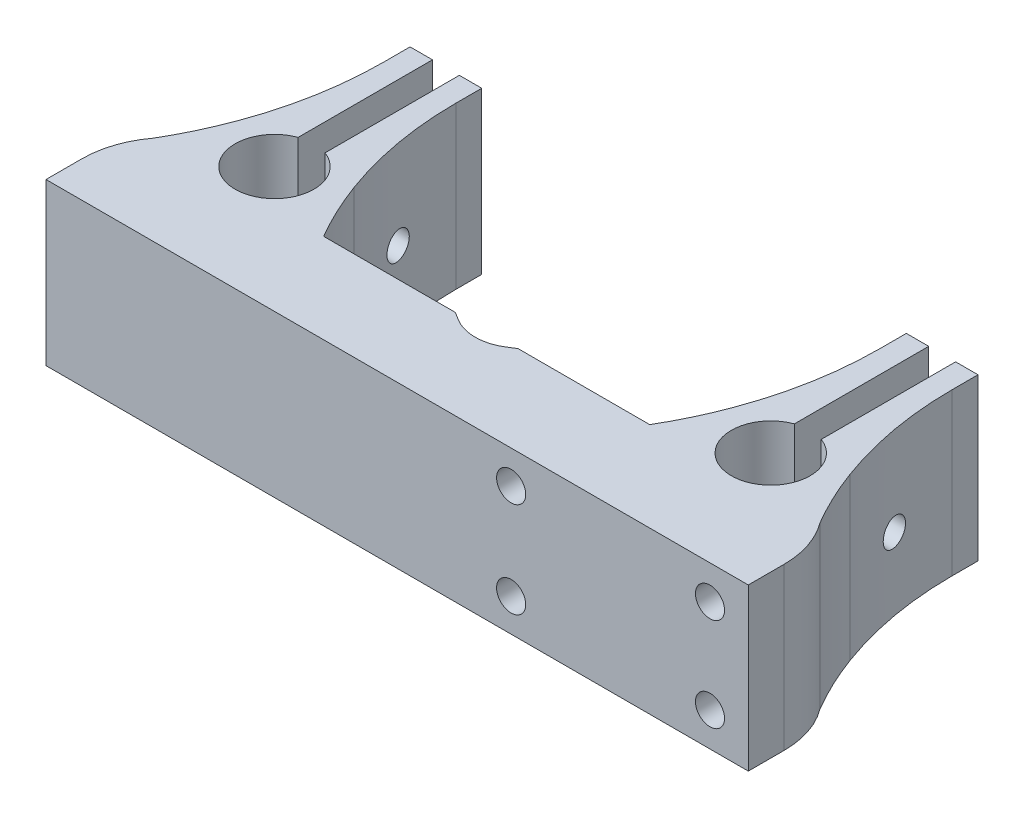
SolidWorks part; units mm, degrees
material "AA356.0-F"
ref_plane "Alzado" through (0, 0, 0) normal (0, 0, 1) x (1, 0, 0)
ref_plane "Planta" through (0, 0, 0) normal (0, 1, 0) x (1, 0, 0)
ref_plane "Vista lateral" through (0, 0, 0) normal (1, 0, 0) x (0, 0, -1)
sketch "Sketch7" plane through (0, 0, 0) normal (0, 1, 0) x (1, 0, 0)
  line L10 (3.5, 0) -> (18.2, 0)
  line L11 (18.2, 0) -> (37.2, 0) construction
  line L12 (27.7, -10) -> (27.7, 2) construction
  line L13 (31.7, 23.1441) -> (29.2, 23.1441)
  line L14 (31.7, 9.63) -> (31.7, 23.1441)
  line L15 (29.2, 23.1441) -> (29.2, 8.1441)
  line L16 (37.2, 0) -> (34.5992, 4.1136)
  line L18 (0, -2.2) -> (3.5, 0)
  line L19 (37.2, 0) -> (39.2, 0)
  line L20 (18.2, 0) -> (20.8008, 4.1136)
  line L21 (23.7, 9.63) -> (23.7, 23.1441)
  line L23 (39.2, -10) -> (0, -10)
  line L24 (0, -10) -> (0, -2.2)
  line L25 (23.7, 23.1441) -> (26.2, 23.1441)
  line L26 (26.2, 23.1441) -> (26.2, 8.1441)
  line L27 (39.2, 0) -> (39.2, -10)
  circle A3 centre (27.7, 4.0077) radius 4.4 construction
  arc A4 (20.8008, 4.1136) -> (23.7, 9.63) centre (27.7, 4.0077) cw
  arc A5 (26.2, 8.1441) -> (29.2, 8.1441) centre (27.7, 4.0077) ccw
  arc A6 (34.5992, 4.1136) -> (31.7, 9.63) centre (27.7, 4.0077) ccw
  circle A9 centre (27.7, 4.0077) radius 4 construction
  point P0 (0, 0)
  dimension "D2" = 0.4
  dimension "D4" = 19
  dimension "D5" = 2.2
  dimension "D6" = 10
  dimension "D8" = 2.5
  dimension "D3" = 3.5
  dimension "D7" = 1.5
  dimension "D9" = 2.5
  dimension "D10" = 15
  dimension "D11" = 2
extrude "Boss-Extrude1" add sketch "Sketch7" along normal blind 18
mirror "Mirror1" about plane through (0, 18, 10) normal (1, 0, 0) of "Boss-Extrude1"
fillet "Fillet1" radius 40 8 edges at (23.7, 9, -9.63) (20.8008, 9, -4.1136) (31.7, 9, -9.63) (34.5992, 9, -4.1136) (-20.8008, 9, -4.1136) (-23.7, 9, -9.63) (-34.5992, 9, -4.1136) (-31.7, 9, -9.63)
fillet "Fillet2" radius 10 2 edges at (-39.2, 9, 0) (39.2, 9, 0)
sketch "Sketch8" plane through (29.2, 0, 0) normal (-1, 0, 0) x (0, 0, 1)
  line L1 (-8.1441, 18) -> (-8.1441, 0) construction
  circle A0 centre (-13.1441, 8.1) radius 1.52
  dimension "D1" = 5
extrude "Cut-Extrude1" cut sketch "Sketch8" against normal through all and the other way through all
fillet "Fillet3" radius 5 1 edges at (0, 9, 2.2)
sketch "Sketch13" plane through (0, 0, 10) normal (0, 0, 1) x (1, 0, 0)
  circle A0 centre (12.725, 3.675) radius 1.625
  circle A1 centre (34.925, 14.225) radius 1.625
extrude "Cut-Extrude6" cut sketch "Sketch13" against normal blind 10
sketch "Sketch14" plane through (0, 0, 10) normal (0, 0, 1) x (1, 0, 0)
  circle A0 centre (12.725, 14.325) radius 1.625
  circle A1 centre (34.925, 3.775) radius 1.625
extrude "Cut-Extrude7" cut sketch "Sketch14" against normal blind 10
